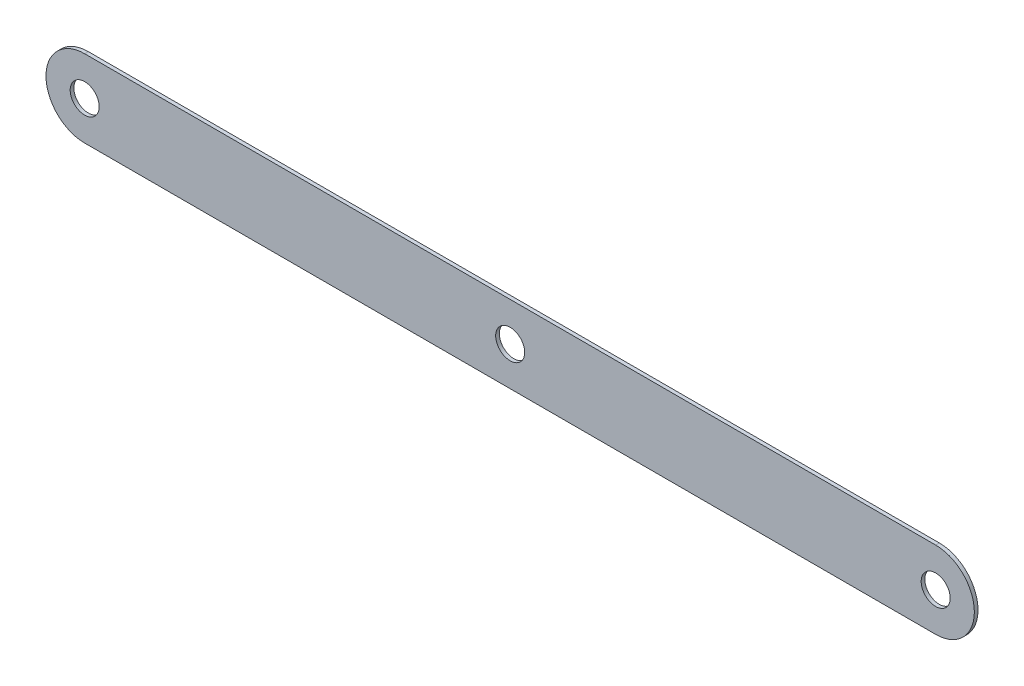
SolidWorks part; units mm, degrees
material "Alloy Steel"
ref_plane "Front" through (0, 0, 0) normal (0, 0, 1) x (1, 0, 0)
ref_plane "Top" through (0, 0, 0) normal (0, 1, 0) x (1, 0, 0)
ref_plane "Right" through (0, 0, 0) normal (1, 0, 0) x (0, 0, -1)
sketch "Sketch1" plane through (0, 0, 0) normal (0, 0, 1) x (1, 0, 0)
  line L1 (-139.7, 12.7) -> (139.7, 12.7)
  line L2 (-139.7, 12.7) -> (-139.7, -12.7)
  line L3 (-139.7, -12.7) -> (139.7, -12.7)
  line L4 (139.7, 12.7) -> (139.7, -12.7)
  line L5 (-139.7, 12.7) -> (139.7, -12.7) construction
  line L6 (-139.7, -12.7) -> (139.7, 12.7) construction
  arc A0 (-139.7, 12.7) -> (-139.7, -12.7) centre (-139.7, 0) ccw
  arc A1 (139.7, 12.7) -> (139.7, -12.7) centre (139.7, 0) cw
  point P0 (0, 0)
  dimension "D3" = 12.7
  dimension "D1" = 279.4
  dimension "D2" = 25.4
extrude "Boss-Extrude1" add sketch "Sketch1" along normal blind 1.2 contours L4 L1 L2 L3 | A1 L4 | L2 A0 region at (0, 0, 0) region at (-145.09, 0, 0) region at (145.09, 0, 0)
sketch "Sketch2" plane through (0, 0, 1.2) normal (0, 0, 1) x (1, 0, 0)
  circle A0 centre (0, 0) radius 4.7625
  dimension "D1" = 9.525
extrude "Cut-Extrude1" cut sketch "Sketch2" against normal through all
sketch "Sketch3" plane through (0, 0, 1.2) normal (0, 0, 1) x (1, 0, 0)
  circle A0 centre (-139.7, 0) radius 4.7625
  circle A1 centre (139.7, 0) radius 4.7625
  dimension "D1" = 9.525
  dimension "D2" = 9.525
extrude "Cut-Extrude2" cut sketch "Sketch3" against normal through all
